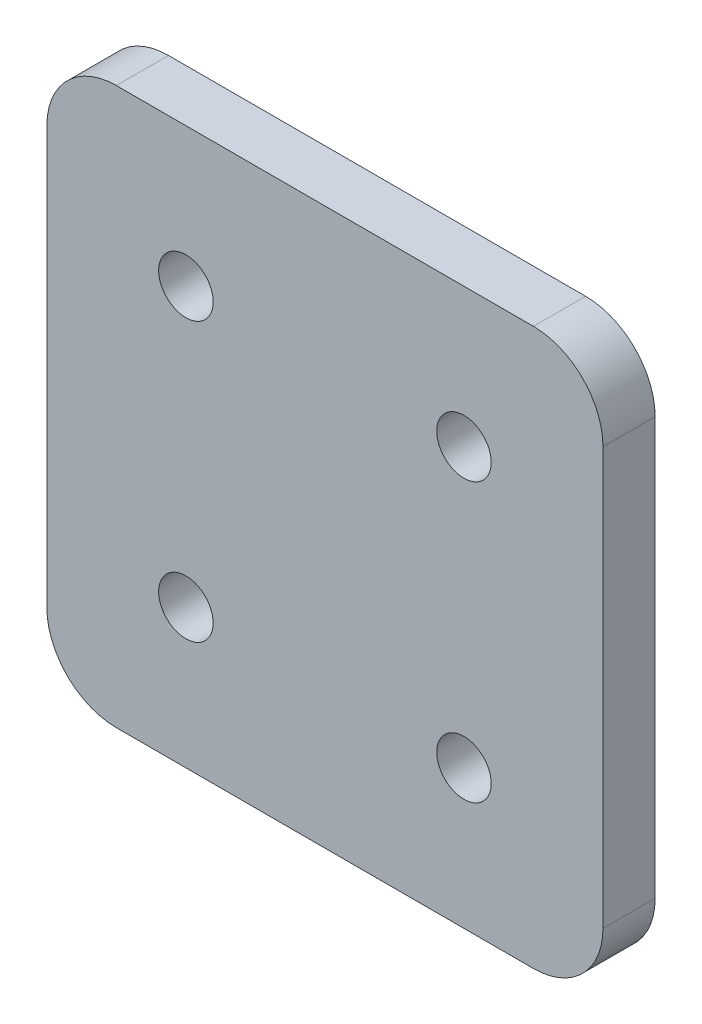
SolidWorks part; units mm, degrees
material "6061-T6 (SS)"
ref_plane "Front Plane" through (0, 0, 0) normal (0, 0, 1) x (1, 0, 0)
ref_plane "Top Plane" through (0, 0, 0) normal (0, 1, 0) x (1, 0, 0)
ref_plane "Right Plane" through (0, 0, 0) normal (1, 0, 0) x (0, 0, -1)
sketch "Sketch2" plane through (0, 0, 0) normal (0, 0, 1) x (1, 0, 0)
  line L1 (0, 0) -> (50.8, 0)
  line L2 (0, 0) -> (0, 50.8)
  line L3 (0, 50.8) -> (50.8, 50.8)
  line L4 (50.8, 0) -> (50.8, 50.8)
  dimension "D1" = 50.8
  dimension "D2" = 50.8
extrude "Boss-Extrude1" add sketch "Sketch2" against normal blind 4.7625
sketch "Sketch3" plane through (0, 0, 0) normal (0, 0, 1) x (1, 0, 0)
  line L0 (50.8, 50.8) -> (0, 50.8) construction
  line L1 (0, 50.8) -> (0, 0) construction
  circle A0 centre (12.7, 38.1) radius 2.4892
  circle A17 centre (38.1, 38.1) radius 2.4892
  circle A41 centre (12.7, 12.7) radius 2.4892
  circle A42 centre (12.7, -12.7) radius 2.4892
  circle A43 centre (38.1, 12.7) radius 2.4892
  circle A44 centre (38.1, -12.7) radius 2.4892
  dimension "D1" = 4.9784
  dimension "D2" = 12.7
  dimension "D3" = 12.7
  dimension "D4" = 3
  dimension "D5" = 2
extrude "Cut-Extrude1" cut sketch "Sketch3" against normal through all
fillet "Fillet1" radius 6.35 4 edges at (0, 0, -2.3813) (50.8, 0, -2.3813) (50.8, 50.8, -2.3813) (0, 50.8, -2.3813)
